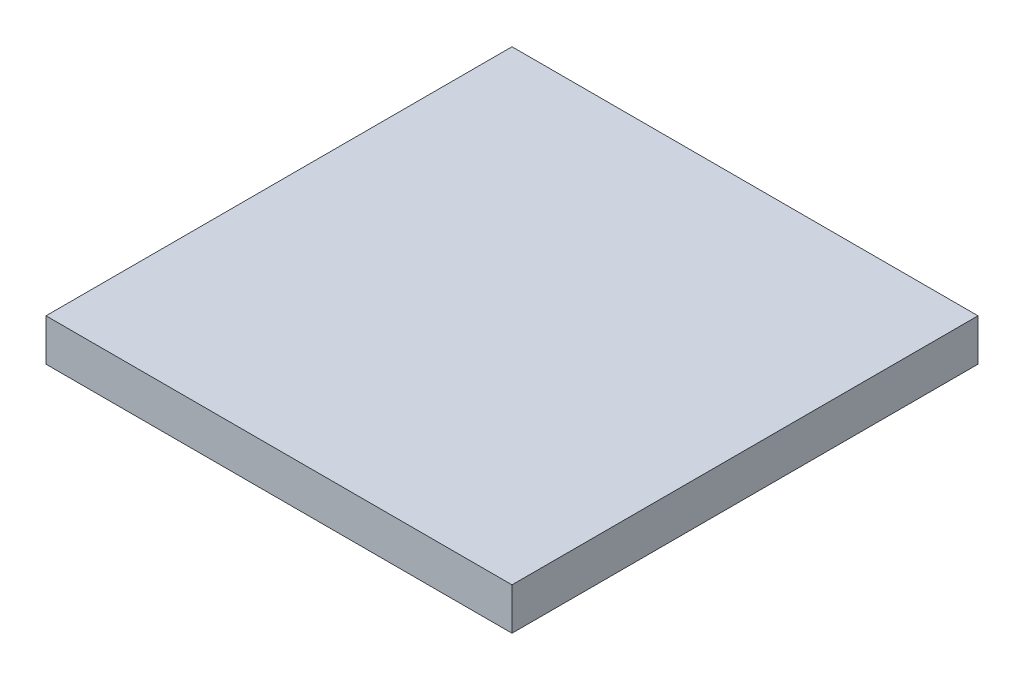
SolidWorks part; units mm, degrees
ref_plane "Front Plane" through (0, 0, 0) normal (0, 0, 1) x (1, 0, 0)
ref_plane "Top Plane" through (0, 0, 0) normal (0, 1, 0) x (1, 0, 0)
ref_plane "Right Plane" through (0, 0, 0) normal (1, 0, 0) x (0, 0, -1)
sketch "Sketch1" plane through (0, 0, 0) normal (0, 1, 0) x (1, 0, 0)
  line L1 (-20, 20) -> (20, 20)
  line L2 (-20, 20) -> (-20, -20)
  line L3 (-20, -20) -> (20, -20)
  line L4 (20, 20) -> (20, -20)
  line L5 (-20, 20) -> (20, -20) construction
  line L6 (-20, -20) -> (20, 20) construction
  point P0 (0, 0)
  dimension "D1" = 40
  dimension "D2" = 40
extrude "Boss-Extrude1" add sketch "Sketch1" along normal mid plane 3.6
sketch "Sketch2" plane through (0, 1.8, 0) normal (0, 1, 0) x (1, 0, 0)
  spline S0 degree 3 poles (-20, -20) (10.358, -40.3225) (-10.5116, -148.7716) (20, -20) knots 0 0 0 0 1 1 1 1
